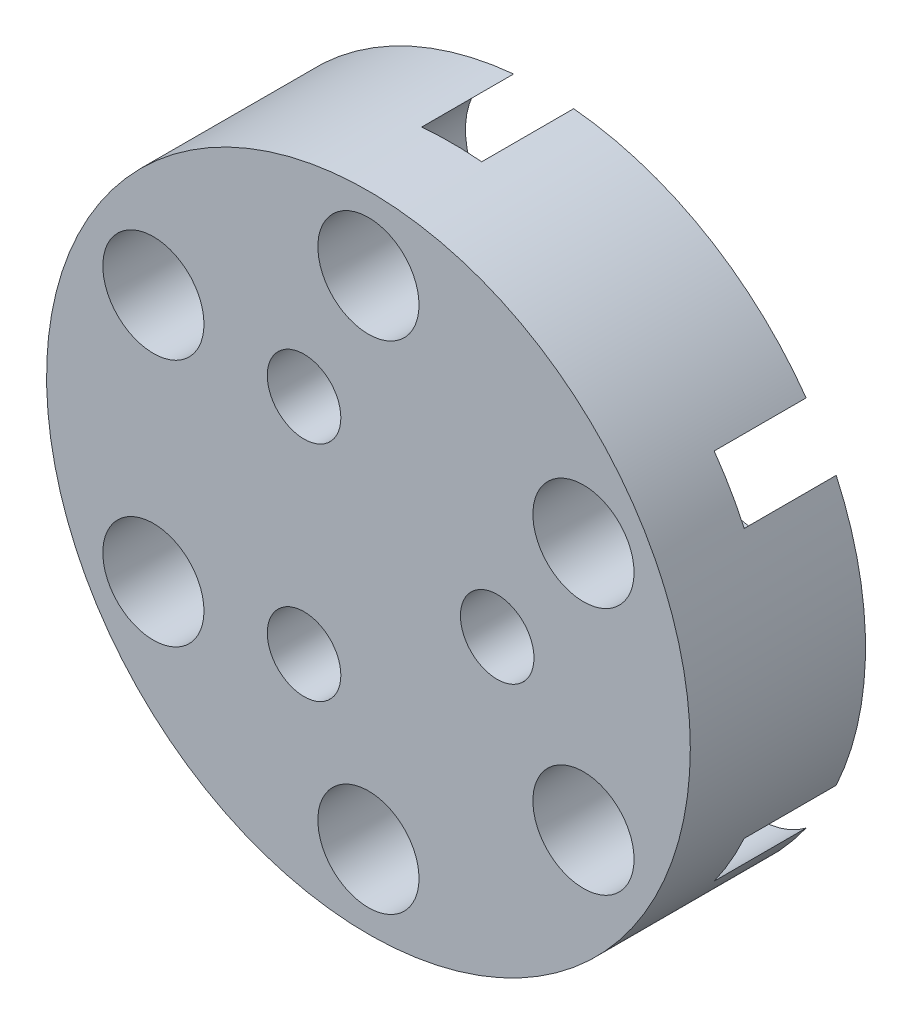
SolidWorks part; units mm, degrees
material "6061 Alloy"
ref_plane "Front Plane" through (0, 0, 0) normal (0, 0, 1) x (1, 0, 0)
ref_plane "Top Plane" through (0, 0, 0) normal (0, 1, 0) x (1, 0, 0)
ref_plane "Right Plane" through (0, 0, 0) normal (1, 0, 0) x (0, 0, -1)
sketch "Sketch1" plane through (0, 0, 0) normal (0, 0, 1) x (1, 0, 0)
  circle A0 centre (0, 0) radius 17.5
  dimension "D1" = 35
extrude "Boss-Extrude1" add sketch "Sketch1" along normal blind 9.525
sketch "Sketch2" plane through (0, 0, 9.525) normal (0, 0, 1) x (1, 0, 0)
  circle A0 centre (0, 0) radius 13.5 construction
  circle A1 centre (0, 13.5) radius 2.75
  circle A2 centre (11.6913, 6.75) radius 2.75
  circle A3 centre (11.6913, -6.75) radius 2.75
  circle A4 centre (0, -13.5) radius 2.75
  circle A5 centre (-11.6913, -6.75) radius 2.75
  circle A6 centre (-11.6913, 6.75) radius 2.75
  point P17 (0, 0)
  dimension "D1" = 27
  dimension "D2" = 5.5
  dimension "D3" = 6
extrude "M5_through" cut sketch "Sketch2" against normal up to surface (9.525 mm away) up to face at (17.5, 0, 0)
sketch "Sketch3" plane through (0, 0, 9.525) normal (0, 0, 1) x (1, 0, 0)
  line L0 (0, 0) -> (-3.5, 6.0622) construction
  line L1 (0, 0) -> (7, 0) construction
  circle A0 centre (0, 0) radius 7 construction
  circle A1 centre (-3.5, 6.0622) radius 2
  circle A2 centre (7, 0) radius 2
  circle A3 centre (-3.5, -6.0622) radius 2
  point P12 (0, 0)
  dimension "D1" = 14
  dimension "D3" = 4
  dimension "D4" = 3
  dimension "D2" = 120
extrude "M4_DRILL" cut sketch "Sketch3" against normal up to surface (9.525 mm away) up to face at (2.75, 13.5, 0)
sketch "Sketch4" plane through (0, 0, 0) normal (0, 0, -1) x (-1, 0, 0)
  circle A0 centre (0, 13.5) radius 4.25
  circle A1 centre (11.6913, 6.75) radius 4.25
  circle A2 centre (11.6913, -6.75) radius 4.25
  circle A3 centre (0, -13.5) radius 4.25
  circle A4 centre (-11.6913, -6.75) radius 4.25
  circle A5 centre (-11.6913, 6.75) radius 4.25
  point P15 (0, 0)
  dimension "D1" = 8.5
  dimension "D2" = 6
extrude "Cut-Extrude2" cut sketch "Sketch4" against normal blind 5
